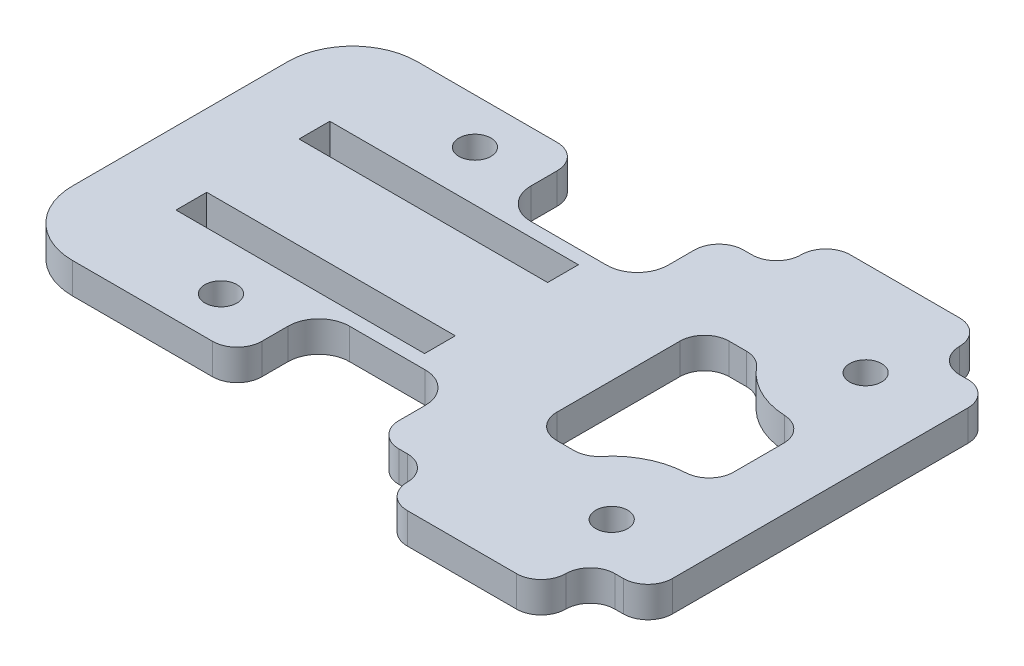
SolidWorks part; units mm, degrees
other "下垫片"
ref_plane "前视基准面" through (0, 0, 0) normal (0, 0, 1) x (1, 0, 0)
ref_plane "上视基准面" through (0, 0, 0) normal (0, 1, 0) x (1, 0, 0)
ref_plane "右视基准面" through (0, 0, 0) normal (1, 0, 0) x (0, 0, -1)
other "Configuration Table"
sketch "草图1" plane through (0, 0, 0) normal (0, 1, 0) x (1, 0, 0)
  line L0 (-89.3251, 0) -> (102.0425, 0) construction
  line L1 (0, 56.7239) -> (0, -62.578) construction
  line L2 (-47.2, -7.5) -> (-6.8, -7.5)
  line L3 (-47.2, 12.5) -> (-6.8, 12.5)
  line L4 (-47.2, 12.5) -> (-47.2, 7.5)
  line L5 (-47.2, 7.5) -> (-6.8, 7.5)
  line L6 (-6.8, 12.5) -> (-6.8, 7.5)
  line L7 (-47.2, 12.5) -> (-6.8, 7.5) construction
  line L8 (-47.2, 7.5) -> (-6.8, 12.5) construction
  line L9 (-6.8, -12.5) -> (-6.8, -7.5)
  line L10 (-47.2, -12.5) -> (-6.8, -12.5)
  line L11 (-47.2, -12.5) -> (-47.2, -7.5)
  line L14 (-21.75, -26.5375) -> (-21.75, -14.7375)
  line L15 (-21.75, -14.7375) -> (0.55, -14.7375)
  line L16 (0.55, -26.5375) -> (0.55, -14.7375)
  line L17 (-21.75, -26.5375) -> (0.55, -14.7375) construction
  line L18 (-21.75, -14.7375) -> (0.55, -26.5375) construction
  line L19 (-21.75, 14.7375) -> (0.55, 14.7375)
  line L20 (0.55, 26.5375) -> (0.55, 14.7375)
  line L22 (-21.75, 26.5375) -> (-21.75, 14.7375)
  line L23 (-21.75, 30.0095) -> (0.55, 30.0095)
  line L25 (-21.75, -26.5375) -> (-21.75, -30.0095)
  line L26 (-21.75, -30.0095) -> (0.55, -30.0095)
  line L27 (0.55, -26.5375) -> (0.55, -30.0095)
  line L28 (0.55, 26.5375) -> (0.55, 30.0095)
  line L30 (-21.75, 26.5375) -> (-21.75, 30.0095)
  circle A0 centre (-31.75, 20.6375) radius 2.6
  circle A4 centre (31.75, 20.6375) radius 2.6
  circle A5 centre (31.75, -20.6375) radius 2.6
  circle A6 centre (-31.75, -20.6375) radius 2.6
  point P13 (-27, 10)
  point P22 (-10.6, -20.6375)
  point P35 (-27, 10)
  dimension "D5" = 5.2
  dimension "D11" = 5.2
  dimension "D1" = 40.4
  dimension "D2" = 31.75
  dimension "D3" = 5
  dimension "D4" = 20.6375
  dimension "D6" = 10
  dimension "D7" = 22.3
  dimension "D8" = 11.8
  dimension "D9" = 0
  dimension "D10" = 31.2
  dimension "D12" = 5
  dimension "D13" = 40.4
  dimension "D14" = 27
  dimension "D15" = 10
  dimension "D16" = 2.2375
sketch "草图3" plane through (0, 0, 0) normal (0, 1, 0) x (1, 0, 0)
  line L0 (-40, 28) -> (-59, 28)
  line L1 (-40, -28) -> (9.9, -28)
  line L3 (-40, 28) -> (9.9, 28)
  line L5 (-40, -28) -> (40, 28) construction
  line L6 (-40, 28) -> (40, -28) construction
  line L7 (-59, 28) -> (-59, -28)
  line L8 (-59, -28) -> (-40, -28)
  line L10 (45, 28) -> (45, -28)
  line L15 (-45.7746, 0) -> (58.2399, 0) construction
  line L19 (9.9, 28) -> (9.9, 36)
  line L20 (9.9, 36) -> (35.65, 36)
  line L21 (35.65, 36) -> (35.65, 28)
  line L22 (35.65, 28) -> (45, 28)
  line L23 (35.65, -28) -> (45, -28)
  line L24 (35.65, -36) -> (35.65, -28)
  line L25 (9.9, -36) -> (35.65, -36)
  line L26 (9.9, -28) -> (9.9, -36)
  point P0 (0, 0)
  dimension "D1" = 56
  dimension "D2" = 80
  dimension "D3" = 19
  dimension "D4" = 5
  dimension "D5" = 9.35
  dimension "D6" = 8
  dimension "D7" = 25.75
extrude "凸台-拉伸1" add sketch "草图3" along normal blind 5
extrude "切除-拉伸1" cut sketch "草图1" along normal up to surface (5 mm away) up to face at (12.85, 5, 0)
fillet "圆角1" radius 5 4 edges at (0.55, 2.5, 14.7375) (-21.75, 2.5, 14.7375) (0.55, 2.5, -14.7375) (-21.75, 2.5, -14.7375)
fillet "圆角2" radius 4 14 edges at (0.55, 2.5, 28) (-21.75, 2.5, 28) (0.55, 2.5, -28) (-21.75, 2.5, -28) (9.9, 2.5, 28) (9.9, 2.5, 36) (35.65, 2.5, 36) (35.65, 2.5, 28) (45, 2.5, 28) (45, 2.5, -28) (35.65, 2.5, -28) (35.65, 2.5, -36) (9.9, 2.5, -36) (9.9, 2.5, -28)
sketch "草图14" plane through (0, 5, 0) normal (0, 1, 0) x (1, 0, 0)
  line L0 (-11.6114, 0) -> (10.899, 0) construction
  line L1 (21.04, 14) -> (12.2, 14)
  line L2 (12.2, 14) -> (12.2, -14)
  line L3 (45, -24) -> (45, 24) construction
  line L4 (35, 8.4639) -> (35, -8.4639)
  line L5 (21.04, -14) -> (12.2, -14)
  arc A0 (35, 8.4639) -> (21.04, 14) centre (31.75, 20.6375) cw
  arc A1 (35, -8.4639) -> (21.04, -14) centre (31.75, -20.6375) ccw
  point P5 (35, 0)
  point P7 (21.04, 14)
  point P8 (35, 8.4639)
  point P18 (12.2, 0)
  dimension "D1" = 12.6
  dimension "D2" = 14
  dimension "D3" = 12.2
  dimension "D4" = 10
extrude "切除-拉伸6" cut sketch "草图14" against normal through all
fillet "圆角5" radius 4 6 edges at (35, 2.5, 8.4639) (21.04, 2.5, 14) (12.2, 2.5, 14) (21.04, 2.5, -14) (35, 2.5, -8.4639) (12.2, 2.5, -14)
fillet "圆角6" radius 10.5 2 edges at (-59, 2.5, 28) (-59, 2.5, -28)
